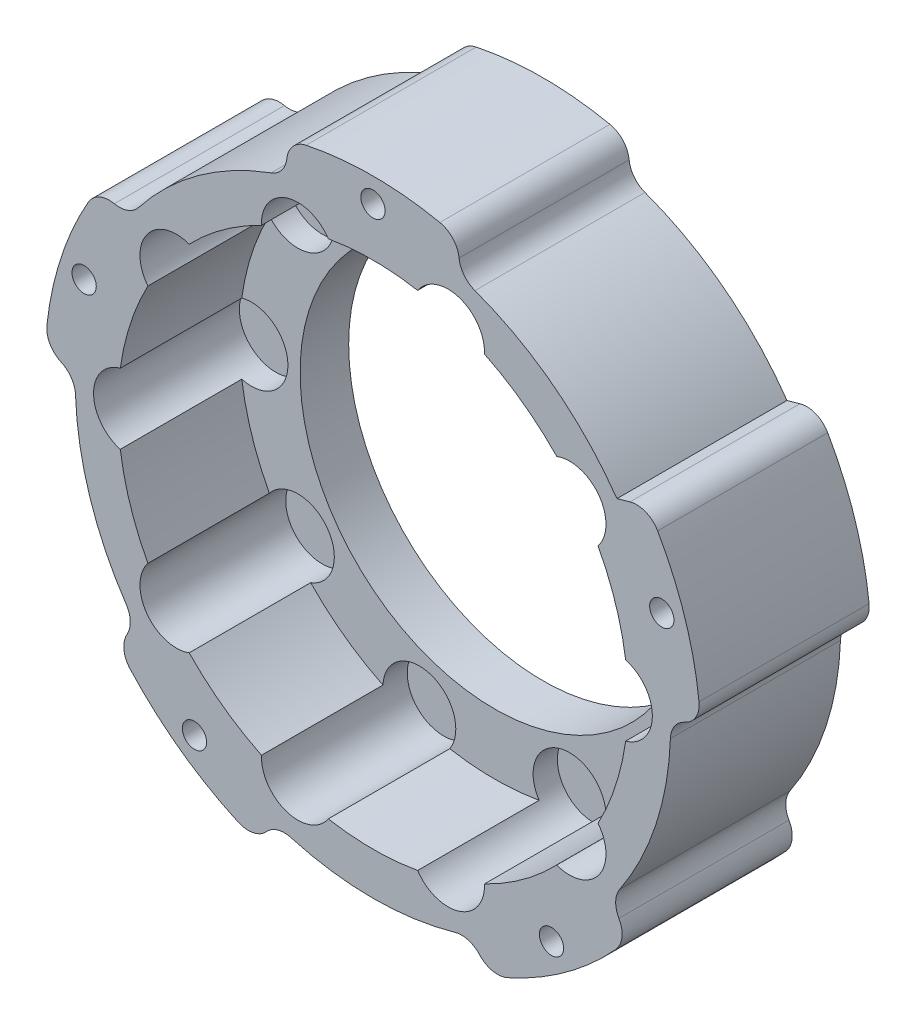
SolidWorks part; units mm, degrees
ref_plane "前视基准面" through (0, 0, 0) normal (0, 0, 1) x (1, 0, 0)
ref_plane "上视基准面" through (0, 0, 0) normal (0, 1, 0) x (1, 0, 0)
ref_plane "右视基准面" through (0, 0, 0) normal (1, 0, 0) x (0, 0, -1)
sketch "草图1" plane through (0, 0, 0) normal (0, 0, 1) x (1, 0, 0)
  circle A0 centre (0, 0) radius 25
  circle A1 centre (0, 0) radius 20 construction
extrude "凸台-拉伸1" add sketch "草图1" along normal blind 2
sketch "草图2" plane through (0, 0, 2) normal (0, 0, 1) x (1, 0, 0)
  circle A0 centre (0, 0) radius 20 construction
  circle A1 centre (20, 0) radius 3
  circle A2 centre (16.1803, -11.7557) radius 3
  circle A3 centre (6.1803, -19.0211) radius 3
  circle A4 centre (-6.1803, -19.0211) radius 3
  circle A5 centre (-16.1803, -11.7557) radius 3
  circle A6 centre (-20, 0) radius 3
  circle A7 centre (-16.1803, 11.7557) radius 3
  circle A8 centre (-6.1803, 19.0211) radius 3
  circle A9 centre (6.1803, 19.0211) radius 3
  circle A10 centre (16.1803, 11.7557) radius 3
  point P25 (0, 0)
  dimension "D1" = 10
extrude "凸台-拉伸2" add sketch "草图2" along normal blind 10
sketch "草图3" plane through (0, 0, 2) normal (0, 0, 1) x (1, 0, 0)
  circle A0 centre (0, 0) radius 16
extrude "切除-拉伸1" cut sketch "草图3" against normal blind 10
sketch "草图4" plane through (0, 0, 12) normal (0, 0, 1) x (1, 0, 0)
  circle A0 centre (6.1803, 19.0211) radius 3 construction
  circle A1 centre (16.1803, 11.7557) radius 3
  circle A2 centre (16.1803, 11.7557) radius 3
  circle A3 centre (-6.1803, 19.0211) radius 3 construction
  circle A4 centre (-16.1803, 11.7557) radius 3 construction
  circle A5 centre (-20, 0) radius 3 construction
  circle A6 centre (-16.1803, -11.7557) radius 3 construction
  circle A7 centre (-6.1803, -19.0211) radius 3 construction
  circle A8 centre (16.1803, -11.7557) radius 3 construction
  circle A9 centre (20, 0) radius 3 construction
  circle A10 centre (6.1803, 19.0211) radius 3
  circle A11 centre (-6.1803, 19.0211) radius 3
  circle A12 centre (-16.1803, 11.7557) radius 3
  circle A13 centre (-20, 0) radius 3
  circle A14 centre (-16.1803, -11.7557) radius 3
  circle A15 centre (-6.1803, -19.0211) radius 3
  circle A16 centre (16.1803, -11.7557) radius 3
  circle A17 centre (20, 0) radius 3
  circle A19 centre (6.1803, -19.0211) radius 3
  circle A20 centre (6.1803, -19.0211) radius 3
  dimension "D1" = 0
  dimension "D2" = 0
extrude "切除-拉伸2" cut sketch "草图4" against normal blind 12
sketch "草图5" plane through (0, 0, 2) normal (0, 0, 1) x (1, 0, 0)
  circle A0 centre (0, 0) radius 21
  circle A1 centre (0, 0) radius 25 construction
  circle A2 centre (0, 0) radius 25
  circle A3 centre (16.1803, -11.7557) radius 3 construction
  circle A4 centre (6.1803, -19.0211) radius 3 construction
  circle A5 centre (-6.1803, -19.0211) radius 3 construction
  circle A6 centre (-16.1803, -11.7557) radius 3 construction
  circle A7 centre (-20, 0) radius 3 construction
  circle A8 centre (-16.1803, 11.7557) radius 3 construction
  circle A9 centre (-6.1803, 19.0211) radius 3 construction
  circle A10 centre (6.1803, 19.0211) radius 3 construction
  circle A11 centre (16.1803, 11.7557) radius 3 construction
  circle A12 centre (20, 0) radius 3 construction
  arc A13 (15.1281, -14.5651) -> (18.5271, -9.8868) centre (16.1803, -11.7557) ccw
  arc A14 (3.6777, -20.6755) -> (9.1774, -18.8885) centre (6.1803, -19.0211) ccw
  arc A15 (-9.1774, -18.8885) -> (-3.6777, -20.6755) centre (-6.1803, -19.0211) ccw
  arc A16 (-18.5271, -9.8868) -> (-15.1281, -14.5651) centre (-16.1803, -11.7557) ccw
  arc A17 (-20.8, 2.8914) -> (-20.8, -2.8914) centre (-20, 0) ccw
  arc A18 (-15.1281, 14.5651) -> (-18.5271, 9.8868) centre (-16.1803, 11.7557) ccw
  arc A19 (-3.6777, 20.6755) -> (-9.1774, 18.8885) centre (-6.1803, 19.0211) ccw
  arc A20 (9.1774, 18.8885) -> (3.6777, 20.6755) centre (6.1803, 19.0211) ccw
  arc A21 (18.5271, 9.8868) -> (15.1281, 14.5651) centre (16.1803, 11.7557) ccw
  arc A22 (20.8, -2.8914) -> (20.8, 2.8914) centre (20, 0) ccw
  circle M5 centre (16.1803, 11.7557) radius 3
  circle M6 centre (6.1803, 19.0211) radius 3
  circle M7 centre (-6.1803, 19.0211) radius 3
  circle M8 centre (-16.1803, 11.7557) radius 3
  circle M9 centre (-20, 0) radius 3
  circle M10 centre (-16.1803, -11.7557) radius 3
  circle M11 centre (-6.1803, -19.0211) radius 3
  circle M12 centre (6.1803, -19.0211) radius 3
  circle M13 centre (16.1803, -11.7557) radius 3
  circle M14 centre (20, 0) radius 3
  circle M15 centre (0, 0) radius 25
extrude "凸台-拉伸3" add sketch "草图5" along normal blind 12 contours A0 M15 M14 M13 M12 M11 M10 M9 M8 M7 M6 M5 region at (-24.2929, 0, 2)
sketch "草图7" plane through (0, 0, 0) normal (0, 0, -1) x (-1, 0, 0)
  circle A0 centre (0, 0) radius 16 construction
  circle A1 centre (0, 0) radius 25
  circle A2 centre (0, 0) radius 25
  circle A3 centre (0, 0) radius 16
  dimension "D1" = 0
extrude "凸台-拉伸4" add sketch "草图7" along normal blind 2
sketch "草图8" plane through (0, 0, 14) normal (0, 0, 1) x (1, 0, 0)
  circle A1 centre (0, 0) radius 25
  circle A2 centre (0, 0) radius 25
  dimension "D1" = 0
extrude "切除-拉伸3" cut sketch "草图8" against normal blind 2
sketch "草图9" plane through (0, 0, 12) normal (0, 0, 1) x (1, 0, 0)
  circle A1 centre (21.8743, -7.1074) radius 1
  circle A2 centre (13.5191, -18.6074) radius 1
  circle A3 centre (0, -23) radius 1
  circle A4 centre (-13.5191, -18.6074) radius 1
  circle A5 centre (-21.8743, -7.1074) radius 1
  circle A6 centre (-21.8743, 7.1074) radius 1
  circle A7 centre (-13.5191, 18.6074) radius 1
  circle A8 centre (0, 23) radius 1
  circle A9 centre (13.5191, 18.6074) radius 1
  circle A10 centre (21.8743, 7.1074) radius 1
  point P29 (0, 0)
  dimension "D1" = 10
extrude "切除-拉伸4" cut sketch "草图9" against normal blind 15
sketch "草图10" plane through (0, 0, 12) normal (0, 0, 1) x (1, 0, 0)
  circle A0 centre (0, 0) radius 27
  circle A1 centre (0, 0) radius 25
extrude "凸台-拉伸5" add sketch "草图10" against normal up to surface (14 mm away) up to face at (20.8743, 7.1074, -2)
sketch "草图11" plane through (0, 0, 12) normal (0, 0, 1) x (1, 0, 0)
  circle A0 centre (-21.8743, 7.1074) radius 1 construction
  circle A1 centre (-21.8743, -7.1074) radius 1 construction
  circle A2 centre (-13.5191, -18.6074) radius 1 construction
  circle A3 centre (0, -23) radius 1 construction
  circle A4 centre (13.5191, -18.6074) radius 1 construction
  circle A5 centre (21.8743, -7.1074) radius 1 construction
  circle A6 centre (13.5191, 18.6074) radius 1 construction
  circle A7 centre (0, 23) radius 1 construction
  circle A8 centre (-13.5191, 18.6074) radius 1 construction
  circle A9 centre (-21.8743, 7.1074) radius 1
  circle A10 centre (-21.8743, -7.1074) radius 1
  circle A11 centre (-13.5191, -18.6074) radius 1
  circle A12 centre (0, -23) radius 1
  circle A13 centre (13.5191, -18.6074) radius 1
  circle A14 centre (21.8743, -7.1074) radius 1
  circle A15 centre (13.5191, 18.6074) radius 1
  circle A16 centre (0, 23) radius 1
  circle A17 centre (-13.5191, 18.6074) radius 1
  circle A18 centre (21.8743, 7.1074) radius 1 construction
  circle A19 centre (21.8743, 7.1074) radius 1
extrude "凸台-拉伸6" add sketch "草图11" against normal up to surface (14 mm away) up to face at (20.8743, 7.1074, -2)
sketch "草图12" plane through (0, 0, 12) normal (0, 0, 1) x (1, 0, 0)
  circle A0 centre (0, 25) radius 1
  circle A1 centre (23.7764, 7.7254) radius 1
  circle A2 centre (14.6946, -20.2254) radius 1
  circle A3 centre (-14.6946, -20.2254) radius 1
  circle A4 centre (-23.7764, 7.7254) radius 1
  point P14 (0, 0)
extrude "切除-拉伸5" cut sketch "草图12" against normal up to surface (14 mm away) up to face at (-16, 0, -2)
sketch "草图13" plane through (0, 0, 12) normal (0, 0, 1) x (1, 0, 0)
  line L10 (-19.5515, -14.7644) -> (-21.0181, -16.9482)
  line L11 (8, -23.1571) -> (9.6237, -25.2266)
  line L12 (-24.4958, 0.4525) -> (-26.9659, 1.3572)
  line L13 (-8, -23.1571) -> (-9.6237, -25.2266)
  line L14 (-20.0835, 14.0322) -> (-22.6136, 14.7521)
  line L15 (-7.1392, 23.4367) -> (-7.0421, 26.0655)
  line L16 (7.1392, 23.4367) -> (7.0421, 26.0655)
  line L17 (20.0835, 14.0322) -> (22.6136, 14.7521)
  line L18 (24.4958, 0.4525) -> (26.9659, 1.3572)
  line L19 (19.5515, -14.7644) -> (21.0181, -16.9482)
  arc A0 (-8, -23.1571) -> (8, -23.1571) centre (0, 0) ccw
  circle A1 centre (0, 0) radius 27 construction
  arc A2 (-8, -25.7876) -> (8, -25.7876) centre (0, 0) ccw
  arc A11 (-24.4958, 0.4525) -> (-19.5515, -14.7644) centre (0, 0) ccw
  arc A12 (-26.9976, -0.3604) -> (-22.0533, -15.5773) centre (0, 0) ccw
  arc A13 (-7.1392, 23.4367) -> (-20.0835, 14.0322) centre (0, 0) ccw
  arc A14 (-8.6854, 25.5649) -> (-21.6297, 16.1603) centre (0, 0) ccw
  arc A15 (20.0835, 14.0322) -> (7.1392, 23.4367) centre (0, 0) ccw
  arc A16 (21.6297, 16.1603) -> (8.6854, 25.5649) centre (0, 0) ccw
  arc A17 (19.5515, -14.7644) -> (24.4958, 0.4525) centre (0, 0) ccw
  arc A18 (22.0533, -15.5773) -> (26.9976, -0.3604) centre (0, 0) ccw
  arc A19 (21.0181, -16.9482) -> (26.9659, 1.3572) centre (0, 0) ccw
  arc A20 (-9.6237, -25.2266) -> (9.6237, -25.2266) centre (0, 0) ccw
  arc A21 (-26.9659, 1.3572) -> (-21.0181, -16.9482) centre (0, 0) ccw
  arc A22 (-7.0421, 26.0655) -> (-22.6136, 14.7521) centre (0, 0) ccw
  arc A23 (22.6136, 14.7521) -> (7.0421, 26.0655) centre (0, 0) ccw
  point P4 (8.8119, -24.1919)
  point P10 (-20.2848, -15.8563)
  point P18 (-21.3486, 14.3921)
  point P25 (7.0907, 24.7511)
  point P26 (0, 0)
  point P35 (25.7308, 0.9049)
  point P42 (0, 0)
  circle M36 centre (0, 0) radius 27
extrude "切除-拉伸7" cut sketch "草图13" against normal blind 22 contours A0 L13 L11 M36 | A17 L19 L18 M36 | A11 L12 L10 M36 | A13 L15 L14 M36 | A15 L17 L16 M36 region at (-24.0294, -7.8076, 12) region at (0, -25.266, 12) region at (-14.851, 20.4406, 12) region at (24.0294, -7.8076, 12) region at (14.851, 20.4406, 12)
fillet "圆角1" radius 2 1 edges at (9.6237, -25.2266, 5)
fillet "圆角2" radius 2 1 edges at (8, -23.1571, 5)
fillet "圆角3" radius 2 9 edges at (-9.6237, -25.2266, 5) (-21.0181, -16.9482, 5) (-26.9659, 1.3572, 5) (-22.6136, 14.7521, 5) (-7.0421, 26.0655, 5) (7.0421, 26.0655, 5) (22.6136, 14.7521, 5) (26.9659, 1.3572, 5) (21.0181, -16.9482, 5)
fillet "圆角4" radius 2 8 edges at (-8, -23.1571, 5) (19.5515, -14.7644, 5) (24.4958, 0.4525, 5) (7.1392, 23.4367, 5) (-7.1392, 23.4367, 5) (-20.0835, 14.0322, 5) (-24.4958, 0.4525, 5) (-19.5515, -14.7644, 5)
